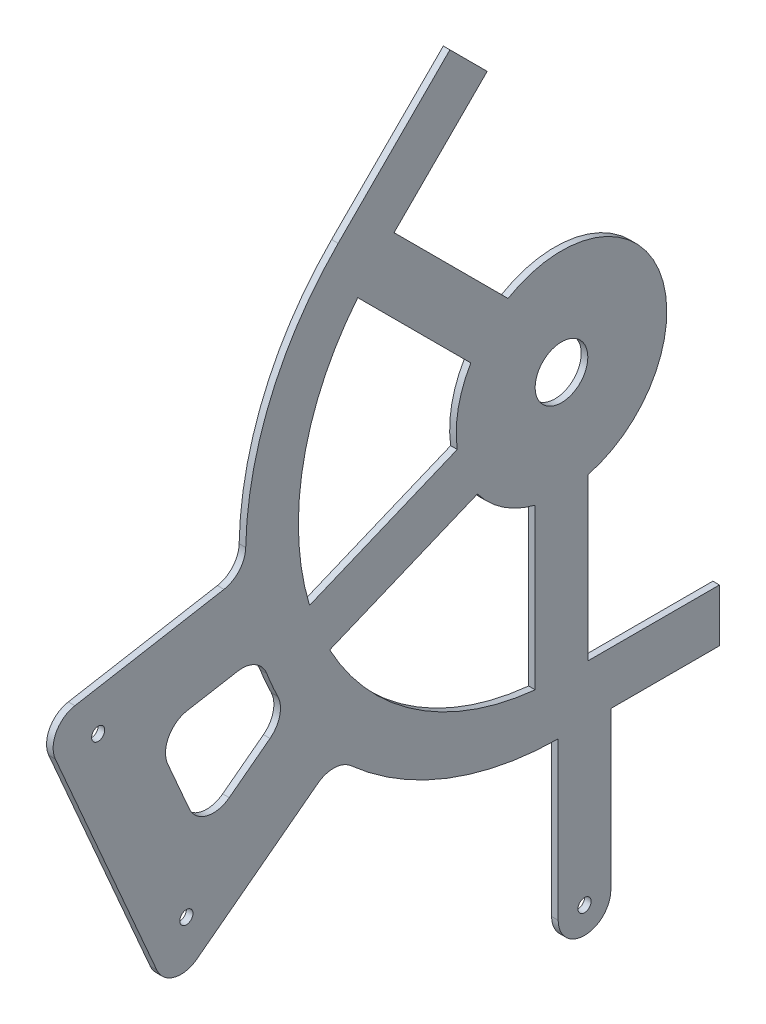
SolidWorks part; units mm, degrees
ref_plane "Front Plane" through (0, 0, 0) normal (0, 0, 1) x (1, 0, 0)
ref_plane "Top Plane" through (0, 0, 0) normal (0, 1, 0) x (1, 0, 0)
ref_plane "Right Plane" through (0, 0, 0) normal (1, 0, 0) x (0, 0, -1)
sketch "Sketch8" plane through (0, 0, 0) normal (1, 0, 0) x (0, 0, -1)
  line L0 (0, 0) -> (-139.7, 0) construction
  circle A1 centre (-272.2355, -114.6296) radius 12.7
  circle A3 centre (-223.5488, -39.2772) radius 3.175
  circle A5 centre (-180.9898, -137.1562) radius 3.175
  circle A7 centre (0, 0) radius 12.7
  circle A9 centre (11.1033, -228.1813) radius 3.175
  circle A10 centre (0, 0) radius 336.7856
  circle A11 centre (0, 0) radius 127
  circle A12 centre (0, 0) radius 152.4
sketch "Sketch9" plane through (0, 0, 0) normal (1, 0, 0) x (0, 0, -1)
  line L0 (0, -126.9544) -> (0, -152.3905)
  line L1 (-89.7703, 89.7703) -> (-107.7564, 107.7564) construction
  line L2 (-98.7633, 98.7633) -> (-44.8818, 152.6449) construction
  line L3 (-107.7564, 107.7564) -> (-53.8406, 161.6722)
  line L4 (-53.8406, 161.6722) -> (-35.8545, 143.6861)
  line L5 (-35.8545, 143.6861) -> (-89.7703, 89.7703)
  arc A0 (-107.7564, 107.7564) -> (0, -152.3905) centre (0, 0) ccw
  arc A1 (-89.7703, 89.7703) -> (0, -126.9544) centre (0, 0) ccw
extrude "Boss-Extrude2" add sketch "Sketch9" along normal blind 3.175
sketch "Sketch11" plane through (0, 0, 0) normal (1, 0, 0) x (0, 0, -1)
  line L0 (0, -152.3905) -> (0, -126.9544) construction
  line L1 (0, -152.3905) -> (0, -126.9544)
  line L2 (0, -126.9544) -> (76.2, -126.9544)
  line L3 (76.2, -126.9544) -> (76.2, -152.3905)
  line L4 (76.2, -152.3905) -> (0, -152.3905)
extrude "Boss-Extrude4" add sketch "Sketch11" along normal blind 3.175
sketch "Sketch12" plane through (0, 0, 0) normal (1, 0, 0) x (0, 0, -1)
  line L0 (11.1033, -228.1813) -> (11.1033, -152.3905) construction
  line L1 (0, -152.3905) -> (76.2, -152.3905) construction
  line L2 (23.8033, -228.1813) -> (23.8033, -152.3905)
  line L3 (-1.5967, -228.1813) -> (-1.5967, -152.3822)
  line L4 (0, -152.3905) -> (23.8033, -152.3905)
  line L5 (-1.5967, -228.1813) -> (-1.5967, -152.3905) construction
  circle A0 centre (11.1033, -228.1813) radius 3.175 construction
  circle A1 centre (11.1033, -228.1813) radius 3.175
  arc A2 (-107.7564, 107.7564) -> (0, -152.3905) centre (0, 0) ccw construction
  arc A3 (-1.5967, -152.3822) -> (0, -152.3905) centre (0, 0) ccw
  arc A4 (23.8033, -228.1813) -> (-1.5717, -227.3844) centre (11.1033, -228.1813) cw
extrude "Boss-Extrude5" add sketch "Sketch12" along normal blind 3.175 contours A4 L2 L4 A3 L3 A1 region at (0, -194.8352, -11.1033)
sketch "Sketch13" plane through (0, 0, 0) normal (1, 0, 0) x (0, 0, -1)
  line L0 (-223.5488, -39.2772) -> (0, 0) construction
  line L1 (-180.9898, -137.1562) -> (0, 0) construction
  line L2 (-180.9898, -137.1562) -> (-223.5488, -39.2772) construction
  line L3 (-175.9217, -157.2176) -> (-117.6154, -113.0324)
  line L4 (-234.7837, -21.9094) -> (-162.8611, -9.2727)
  line L5 (-195.2389, -152.1598) -> (-244.2327, -39.4819)
  line L6 (-160.3069, -97.5804) -> (-140.627, -82.6667)
  line L7 (-180.5603, -51.066) -> (-156.268, -46.7979)
  line L8 (-179.6241, -92.5226) -> (-190.0092, -68.6385)
  line L9 (-250.6605, -24.6989) -> (74.2878, 32.3941) construction
  line L10 (-188.7972, -166.9748) -> (74.2878, 32.3941) construction
  line L11 (-173.1824, -107.3376) -> (-74.2878, -32.3941) construction
  line L12 (-196.437, -53.8555) -> (-74.2878, -32.3941) construction
  line L13 (-173.1824, -107.3376) -> (-196.437, -53.8555) construction
  line L14 (-188.7972, -166.9748) -> (-250.6605, -24.6989) construction
  circle A0 centre (-180.9898, -137.1562) radius 3.175 construction
  circle A2 centre (-223.5488, -39.2772) radius 3.175 construction
  circle A3 centre (-180.9898, -137.1562) radius 3.175
  circle A5 centre (-223.5488, -39.2772) radius 3.175
  arc A6 (-107.7564, 107.7564) -> (-1.5967, -152.3822) centre (0, 0) ccw construction
  arc A9 (-180.5603, -51.066) -> (-190.0092, -68.6385) centre (-178.3625, -63.5744) ccw
  arc A10 (-160.3069, -97.5804) -> (-179.6241, -92.5226) centre (-167.9775, -87.4585) cw
  arc A11 (-175.9217, -157.2176) -> (-195.2389, -152.1598) centre (-183.5923, -147.0957) cw
  arc A12 (-234.7837, -21.9094) -> (-244.2327, -39.4819) centre (-232.586, -34.4178) ccw
  arc A13 (-152.3613, 2.9868) -> (-142.218, -54.744) centre (0, 0) ccw
  arc A14 (-136.8893, -66.9641) -> (-101.4871, -113.6804) centre (0, 0) ccw
  arc A15 (-117.6154, -113.0324) -> (-101.4871, -113.6804) centre (-109.9449, -123.1544) cw
  arc A16 (-140.627, -82.6667) -> (-136.8893, -66.9641) centre (-148.2975, -72.5448) ccw
  arc A17 (-156.268, -46.7979) -> (-142.218, -54.744) centre (-154.0703, -59.3063) cw
  arc A18 (-162.8611, -9.2727) -> (-152.3613, 2.9868) centre (-165.0588, 3.2357) ccw
  dimension "D1" = 12.7
  dimension "D2" = 12.7
extrude "Boss-Extrude6" add sketch "Sketch13" along normal blind 3.175
sketch "Sketch14" plane through (0, 0, 0) normal (1, 0, 0) x (0, 0, -1)
  line L0 (0, 0) -> (-117.2906, -48.5833) construction
  line L1 (0, 0) -> (0, -126.9544) construction
  line L2 (0, 0) -> (-89.7703, 89.7703) construction
  line L3 (-25.8001, 43.7606) -> (-80.79, 98.7506)
  line L4 (76.2, -126.9544) -> (0, -126.9544) construction
  line L5 (12.7, -126.9544) -> (0, -126.9544)
  line L6 (-89.7703, 89.7703) -> (-35.8545, 143.6861) construction
  line L7 (-89.7703, 89.7703) -> (-80.79, 98.7506)
  line L8 (12.7, -49.1869) -> (12.7, -126.9544)
  line L9 (12.7, 0) -> (12.7, -126.9544) construction
  line L10 (-12.7, -49.1869) -> (-12.7, -126.3176)
  line L12 (-40.5827, -30.5563) -> (-111.8421, -60.0729)
  line L14 (-50.3028, -7.0897) -> (-121.5623, -36.6064)
  line L16 (-43.7606, 25.8001) -> (-98.3003, 80.3397)
  line L18 (8.9803, 8.9803) -> (-80.79, 98.7506) construction
  circle A0 centre (0, 0) radius 12.7 construction
  circle A1 centre (0, 0) radius 12.7
  arc A2 (-89.7703, 89.7703) -> (0, -126.9544) centre (0, 0) ccw construction
  arc A3 (-40.5827, -30.5563) -> (-12.7, -49.1869) centre (0, 0) ccw
  arc A4 (12.7, -49.1869) -> (-25.8001, 43.7606) centre (0, 0) ccw
  arc A5 (-43.7606, 25.8001) -> (-50.3028, -7.0897) centre (0, 0) ccw
  arc A6 (-89.7703, 89.7703) -> (-98.3003, 80.3397) centre (0, 0) ccw
  arc A7 (-121.5623, -36.6064) -> (-111.8421, -60.0729) centre (0, 0) ccw
  arc A8 (-12.7, -126.3176) -> (0, -126.9544) centre (0, 0) ccw
extrude "Boss-Extrude7" add sketch "Sketch14" along normal blind 3.175
